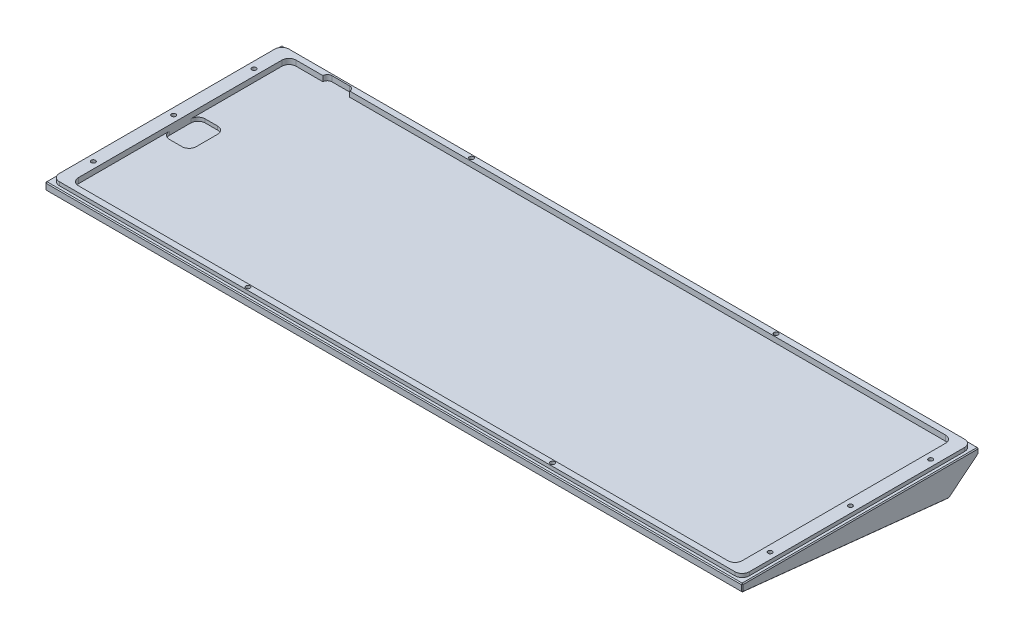
SolidWorks part; units mm, degrees
ref_plane "Front Plane" through (0, 0, 0) normal (0, 0, 1) x (1, 0, 0)
ref_plane "Top Plane" through (0, 0, 0) normal (0, 1, 0) x (1, 0, 0)
ref_plane "Right Plane" through (0, 0, 0) normal (1, 0, 0) x (0, 0, -1)
sketch "Sketch1" plane through (0, 0, 0) normal (0, 1, 0) x (1, 0, 0)
  line L1 (0, 0) -> (390.7, 0)
  line L2 (0, 0) -> (0, 132.7)
  line L3 (0, 132.7) -> (390.7, 132.7)
  line L4 (390.7, 0) -> (390.7, 132.7)
  dimension "D1" = 390.7
  dimension "D2" = 132.7
extrude "MainBody" add sketch "Sketch1" along normal blind 18.5
sketch "Sketch2" plane through (0, 18.5, 0) normal (0, 1, 0) x (1, 0, 0)
  line L0 (390.7, 132.7) -> (0, 132.7) construction
  line L1 (2, 130.7) -> (388.7, 130.7)
  line L2 (2, 130.7) -> (2, 2)
  line L3 (2, 2) -> (388.7, 2)
  line L4 (388.7, 130.7) -> (388.7, 2)
  line L5 (0, 132.7) -> (0, 0) construction
  line L7 (0, 132.7) -> (390.7, 132.7)
  line L8 (0, 132.7) -> (0, 0)
  line L9 (0, 0) -> (390.7, 0)
  line L10 (390.7, 132.7) -> (390.7, 0)
  point P4 (195.35, 130.7)
  point P7 (195.35, 132.7)
  point P8 (2, 66.35)
  point P11 (0, 66.35)
  line M5 (0, 132.7) -> (0, 0)
  line M6 (0, 0) -> (390.7, 0)
  line M7 (390.7, 0) -> (390.7, 132.7)
  line M8 (390.7, 132.7) -> (0, 132.7)
  dimension "D1" = 2
  dimension "D2" = 2
extrude "AligmentLip" cut sketch "Sketch2" against normal blind 2 contours L1 L4 L3 L2 M8 M5 M6 M7 region at (195.35, 18.5, -132.2874)
sketch "Sketch3" plane through (0, 0, 0) normal (-1, 0, 0) x (0, 0, 1)
  line L0 (-132.7, 13.5) -> (-116.0289, 0)
  line L1 (-132.7, 16.5) -> (-132.7, 0) construction
  line L2 (-132.7, 0) -> (0, 0) construction
  line L3 (-116.0289, 0) -> (0, 12.1951)
  line L4 (0, 16.5) -> (0, 0) construction
  line L5 (-132.7, 16.5) -> (0, 16.5) construction
  line L7 (-132.7, 16.5) -> (0, 16.5)
  line L8 (-132.7, 16.5) -> (-132.7, 0)
  line L9 (-132.7, 0) -> (0, 0)
  line L10 (0, 16.5) -> (0, 0)
  line M4 (-132.7, 16.5) -> (-132.7, 0)
  line M5 (-132.7, 0) -> (0, 0)
  line M6 (0, 0) -> (0, 16.5)
  dimension "D1" = 6
  dimension "D2" = 135
  dimension "D3" = 3
extrude "TypingAngle" cut sketch "Sketch3" against normal through all contours L0 M4 M5 | L3 M5 M6 region at (0, 4.5, -127.143) region at (0, 4.065, -38.6763)
sketch "Sketch4" plane through (0, 18.5, 0) normal (0, 1, 0) x (1, 0, 0)
  line L0 (2, 130.7) -> (388.7, 130.7) construction
  line L1 (9.35, 127.35) -> (381.35, 127.35)
  line L2 (9.35, 127.35) -> (9.35, 5.35)
  line L3 (9.35, 5.35) -> (381.35, 5.35)
  line L4 (381.35, 127.35) -> (381.35, 5.35)
  line L5 (2, 130.7) -> (2, 2) construction
  point P4 (195.35, 127.35)
  point P7 (195.35, 130.7)
  point P8 (9.35, 66.35)
  point P11 (2, 66.35)
  dimension "D1" = 372
  dimension "D2" = 122
extrude "PCBCutout" cut sketch "Sketch4" against normal blind 3
sketch3d "3DSketch2"
  line L1 (390.7, 0, -116.0289) -> (390.7, 12.1951, 0) construction
  line L3 (390.7, 7.5626, -100.812) -> (390.7, 1.3066, -103.5974)
  line L6 (390.7, 8.5366, -34.8083) -> (390.7, 10.4246, -37.1397)
  line L9 (390.7, 12.6516, -43.2584) -> (390.7, 13.4937, -91.502)
  arc A0 (390.7, 10.4246, -37.1397) -> (390.7, 12.6516, -43.2584) centre (390.7, 2.6531, -43.4329) cw
  arc A1 (390.7, 7.5626, -100.812) -> (390.7, 13.4937, -91.502) centre (390.7, 3.4952, -91.6766) cw
  point P10 (380.7, 2.6531, -43.4329)
  point P12 (400.7, 3.4952, -91.6766)
  dimension "D1" = 10
  dimension "D2" = 10
  dimension "D3" = 3
  dimension "D4" = 7
  dimension "D5" = 135
  dimension "D6" = 35
  dimension "D8" = 12.5
  dimension "D7" = 60
sketch "Sketch5" plane through (0, 12.0619, -1.2678) normal (0, -0.9945, 0.1045) x (1, 0, 0)
  line L0 (390.7, -33.7253) -> (388.5787, -35.8466)
  line L1 (385.7243, -41.699) -> (379.844, -89.5903)
  line L2 (384.7694, -99.4693) -> (390.7, -102.8933)
  line L3 (390.7, -115.3933) -> (390.7, 1.2747) construction
  arc A0 (388.5787, -35.8466) -> (385.7243, -41.699) centre (395.6497, -42.9177) ccw
  arc A1 (379.844, -89.5903) -> (384.7694, -99.4693) centre (389.7694, -90.809) ccw
  dimension "D3" = 10
  dimension "D4" = 10
  dimension "D1" = 7
  dimension "D2" = 3
  dimension "D5" = 60
  dimension "D6" = 45
sketch3d "3DSketch3"
  line L0 (390.7, 13.4937, -91.502) -> (379.844, 2.6971, -90.3673)
  line L1 (390.7, 12.6516, -43.2584) -> (385.7243, 7.7032, -42.7383)
loft "RightCutout" [suppressed] cut section "Sketch5" section "3DSketch2"
sketch3d "Centerline" [suppressed]
  line L0 (195.35, 15.5, -127.35) -> (195.35, 18.5, -5.35) construction
  line L1 (381.35, 15.5, -127.35) -> (9.35, 15.5, -127.35) construction
  line L2 (9.35, 18.5, -5.35) -> (381.35, 18.5, -5.35) construction
ref_plane "CenterMirrorPlane" [suppressed] through (195.35, 0, 0) normal (-1, 0, 0) x (0, 0, 1)
sketch "Sketch6" plane through (0, 18.5, 0) normal (0, 1, 0) x (1, 0, 0)
  line L0 (390.7, 132.7) -> (0, 132.7) construction
  line L1 (195.35, 132.7) -> (0, 132.7)
  line L2 (195.35, 132.7) -> (195.35, 0)
  line L3 (195.35, 0) -> (0, 0)
  line L4 (0, 132.7) -> (0, 0)
extrude "HalfBodyRemove" [suppressed] cut sketch "Sketch6" against normal through all
mirror "LeftCutout" [suppressed] about plane through (195.35, 0, 0) normal (-1, 0, 0) of bodies 113
sketch "Sketch8" plane through (0, 18.5, 0) normal (0, 1, 0) x (1, 0, 0)
  line L0 (195.35, 132.7) -> (195.35, 0) construction
  line L1 (390.7, 132.7) -> (0, 132.7) construction
  line L2 (0, 0) -> (390.7, 0) construction
  line L3 (0, 66.35) -> (195.35, 66.35) construction
  line L4 (0, 132.7) -> (0, 0) construction
  line L5 (2, 130.7) -> (388.7, 130.7) construction
  line L6 (2, 2) -> (388.7, 2) construction
  line L7 (2, 130.7) -> (2, 2) construction
  point P11 (110, 129)
  point P12 (5.7, 111.35)
  point P13 (5.7, 66.35)
  point P14 (5.7, 21.35)
  point P16 (110, 3.7)
  point P27 (280.7, 3.7)
  point P28 (385, 21.35)
  point P29 (385, 66.35)
  point P30 (385, 111.35)
  point P31 (280.7, 129)
  dimension "D1" = 1.7
  dimension "D2" = 1.7
  dimension "D3" = 110
  dimension "D4" = 45
  dimension "D5" = 45
  dimension "D6" = 3.7
hole_wizard "M2 Clearance Hole2" positions "3DSketch7" profile "Sketch10" hole size "M2" standard "ANSI Metric" end condition through all
sketch3d "3DSketch7"
  point P0 (110, 18.5, -129)
  point P3 (5.7, 18.5, -111.35)
  point P6 (5.7, 18.5, -66.35)
  point P9 (5.7, 18.5, -21.35)
  point P12 (110, 18.5, -3.7)
  point P15 (280.7, 18.5, -129)
  point P18 (280.7, 18.5, -3.7)
  point P21 (385, 18.5, -21.35)
  point P24 (385, 18.5, -66.35)
  point P27 (385, 18.5, -111.35)
sketch "Sketch10" plane through (110, 18.5, -129) normal (1, 0, 0) x (0, 0, 1)
  line L0 (0, 0) -> (0, 18.5)
  line L1 (0, 18.5) -> (1.2, 18.5)
  line L2 (1.2, 18.5) -> (1.2, 0)
  line L5 (1.2, 0) -> (0, 0)
  line L11 (0, -6.35) -> (0, 107.95) construction
  dimension "Thru Hole Dia." = 2.4
  dimension "Thru Hole Depth" = 18.5
sketch "Sketch11" plane through (0, 15.5, 0) normal (0, 1, 0) x (1, 0, 0)
  line L0 (195.35, 132.7) -> (195.35, 0) construction
  line L1 (0, 0) -> (390.7, 0) construction
  circle A0 centre (110, 129) radius 2.5
  circle A1 centre (5.7, 111.35) radius 2.5
  circle A2 centre (5.7, 66.35) radius 2.5
  circle A3 centre (5.7, 21.35) radius 2.5
  circle A4 centre (110, 3.7) radius 2.5
  circle A5 centre (280.7, 3.7) radius 2.5
  circle A6 centre (385, 21.35) radius 2.5
  circle A7 centre (385, 66.35) radius 2.5
  circle A8 centre (385, 111.35) radius 2.5
  circle A9 centre (280.7, 129) radius 2.5
  dimension "D1" = 5
extrude "Cut-Extrude2" cut sketch "Sketch11" against normal through all from offset 1 offset against normal yes
sketch "Sketch12" plane through (0, 18.5, 0) normal (0, 1, 0) x (1, 0, 0)
  line L0 (381.35, 127.35) -> (9.35, 127.35) construction
  line L1 (28.4, 127.35) -> (43.4, 127.35)
  line L2 (28.4, 127.35) -> (28.4, 129.85)
  line L3 (28.4, 129.85) -> (43.4, 129.85)
  line L4 (43.4, 127.35) -> (43.4, 129.85)
  line L5 (0, 132.7) -> (0, 0) construction
  point P6 (35.9, 129.85)
  dimension "D1" = 15
  dimension "D2" = 2.5
  dimension "D3" = 35.9
extrude "Cut-Extrude3" cut sketch "Sketch12" against normal up to surface (3 mm away) up to face at (195.35, 15.5, -66.35)
fillet "Fillet1" radius 2.5 2 edges at (43.4, 17, -129.85) (28.4, 17, -129.85)
sketch "Sketch13" plane through (0, 15.5, 0) normal (0, 1, 0) x (1, 0, 0)
  line L0 (9.35, 127.35) -> (9.35, 5.35) construction
  line L1 (9.35, 76.35) -> (24.35, 76.35)
  line L2 (9.35, 76.35) -> (9.35, 56.35)
  line L3 (9.35, 56.35) -> (24.35, 56.35)
  line L4 (24.35, 76.35) -> (24.35, 56.35)
  line L5 (2, 130.7) -> (2, 2) construction
  point P6 (9.35, 66.35)
  point P9 (2, 66.35)
  dimension "D1" = 15
  dimension "D2" = 20
extrude "Cut-Extrude4" cut sketch "Sketch13" against normal blind 2
fillet "Fillet2" radius 4 12 edges at (381.35, 17, -127.35) (388.7, 17.5, -130.7) (388.7, 17.5, -2) (381.35, 17, -5.35) (9.35, 17, -5.35) (2, 17.5, -2) (9.35, 17, -127.35) (2, 17.5, -130.7) (9.35, 14.5, -56.35) (24.35, 14.5, -56.35) (9.35, 14.5, -76.35) (24.35, 14.5, -76.35)
chamfer "Chamfer1" distance 0.5 angle 45 13 edges at (195.35, 12.1951, 0) (390.7, 15, -132.7) (0, 15, -132.7) (0, 6.75, -124.3644) (390.7, 6.75, -124.3644) (390.7, 6.0976, -58.0144) (390.7, 14.3476, 0) (0, 6.0976, -58.0144) (0, 14.3476, 0) (0, 16.5, -66.35) (195.35, 16.5, 0) (390.7, 16.5, -66.35) (195.35, 16.5, -132.7) first distance on face at (195.35, 14.3476, 0) first distance on face at (195.35, 15, -132.7) first distance on face at (280.7, 12.5283, -131.5) first distance on face at (385, 0.7545, -108.85) first distance on face at (0, 11.739, -76.2858) first distance on face at (390.7, 11.739, -76.2858)
